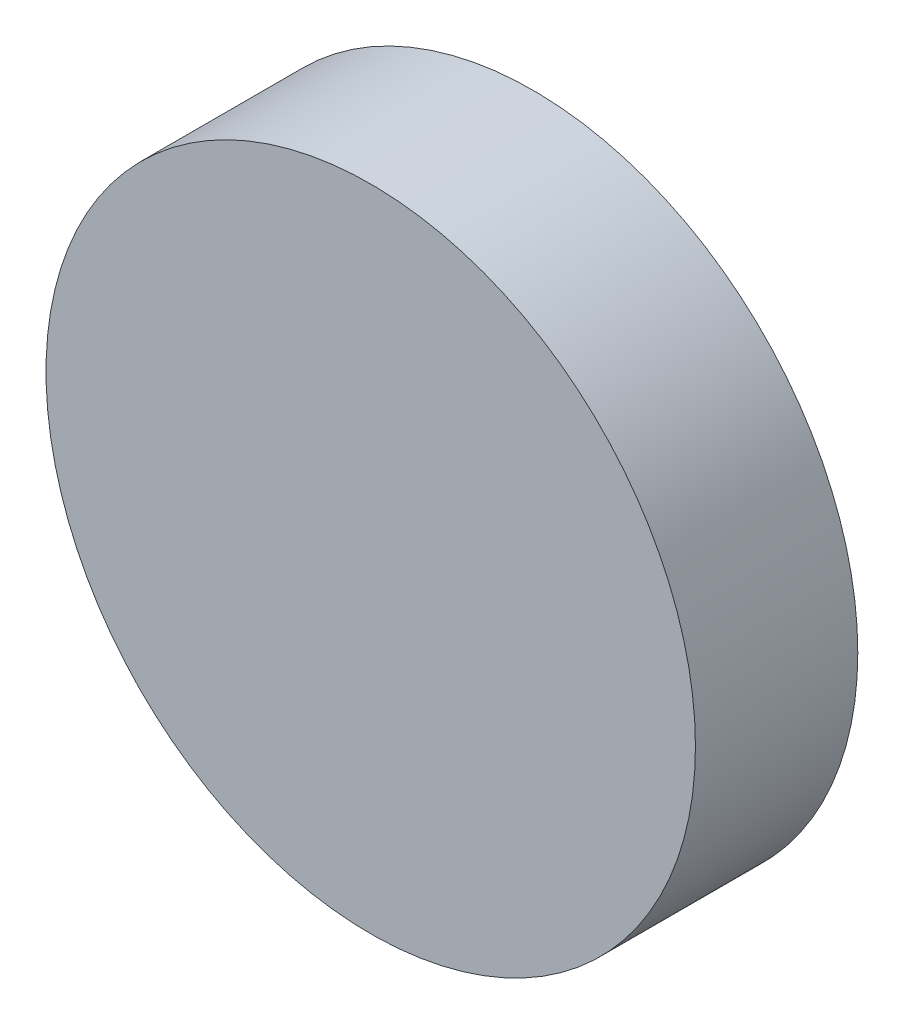
SolidWorks part; units mm, degrees
ref_plane "Front Plane" through (0, 0, 0) normal (0, 0, 1) x (1, 0, 0)
ref_plane "Top Plane" through (0, 0, 0) normal (0, 1, 0) x (1, 0, 0)
ref_plane "Right Plane" through (0, 0, 0) normal (1, 0, 0) x (0, 0, -1)
sketch "Sketch1" plane through (0, 0, 0) normal (0, 0, 1) x (1, 0, 0)
  circle A0 centre (0, 0) radius 7.5
  circle A1 centre (0, 0) radius 10
  dimension "D1" = 15
  dimension "D2" = 20
extrude "Boss-Extrude1" add sketch "Sketch1" along normal blind 5 contours A1
extrude "Cut-Extrude1" cut sketch "Sketch1<3>" along normal blind 3 contours A0
sketch "Sketch1<3>" plane through (0, 0, 0) normal (0, 0, 1) x (1, 0, 0) same geometry as "Sketch1"
